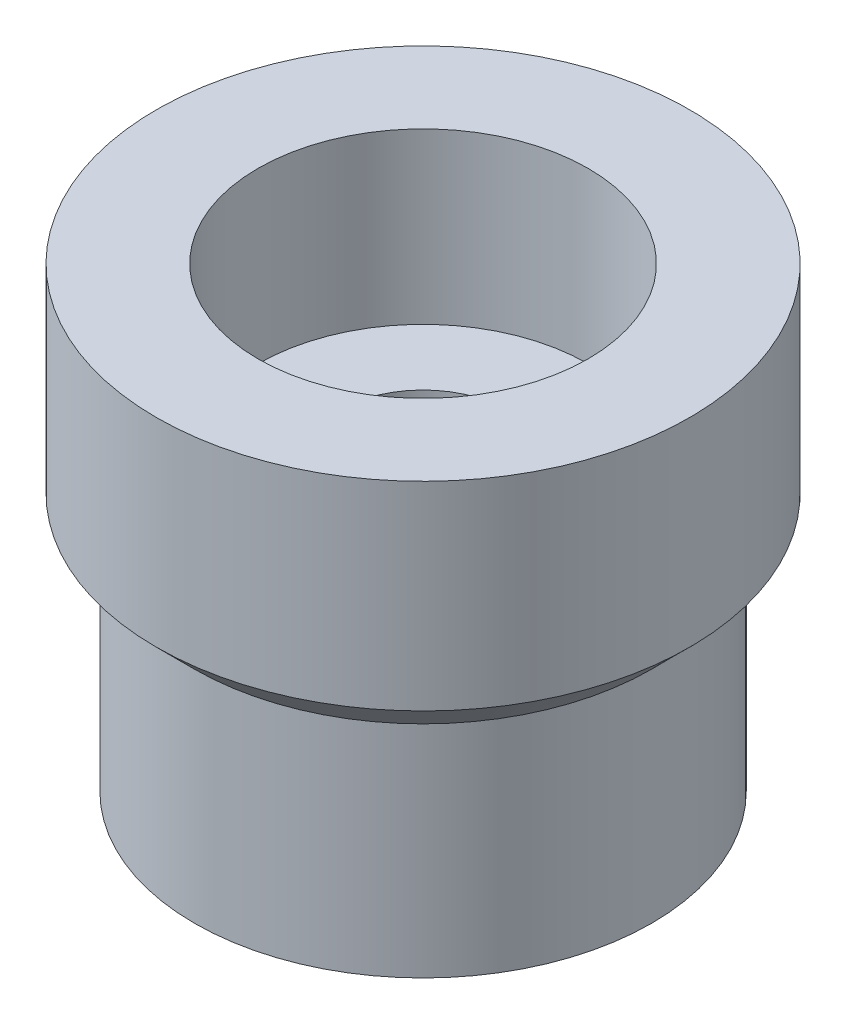
SolidWorks part; units mm, degrees
ref_plane "Спереди" through (0, 0, 0) normal (0, 0, 1) x (1, 0, 0)
ref_plane "Сверху" through (0, 0, 0) normal (0, 1, 0) x (1, 0, 0)
ref_plane "Справа" through (0, 0, 0) normal (1, 0, 0) x (0, 0, -1)
sketch "Эскиз1" plane through (0, 0, 0) normal (0, 1, 0) x (1, 0, 0)
  circle A0 centre (0, 0) radius 1.5
  circle A1 centre (0, 0) radius 2.7
  dimension "D1" = 3
  dimension "D2" = 5.4
extrude "Бобышка-Вытянуть1" add sketch "Эскиз1" along normal blind 2.6
sketch "Эскиз2" plane through (0, 2.6, 0) normal (0, 1, 0) x (1, 0, 0)
  circle A0 centre (0, 0) radius 2.7 construction
  circle A1 centre (0, 0) radius 2.7
  circle A2 centre (0, 0) radius 1
  dimension "D1" = 2
extrude "Бобышка-Вытянуть2" add sketch "Эскиз2" along normal blind 0.8
sketch "Эскиз3" plane through (0, 3.4, 0) normal (0, 1, 0) x (1, 0, 0)
  circle A0 centre (0, 0) radius 3.15
  circle A1 centre (0, 0) radius 1.95
  dimension "D1" = 3.9
  dimension "D2" = 1.2
extrude "Бобышка-Вытянуть3" add sketch "Эскиз3" along normal blind 2
chamfer "Фаска1" distance 0.8 angle 45 1 edges at (0, 3.4, 2.7)
